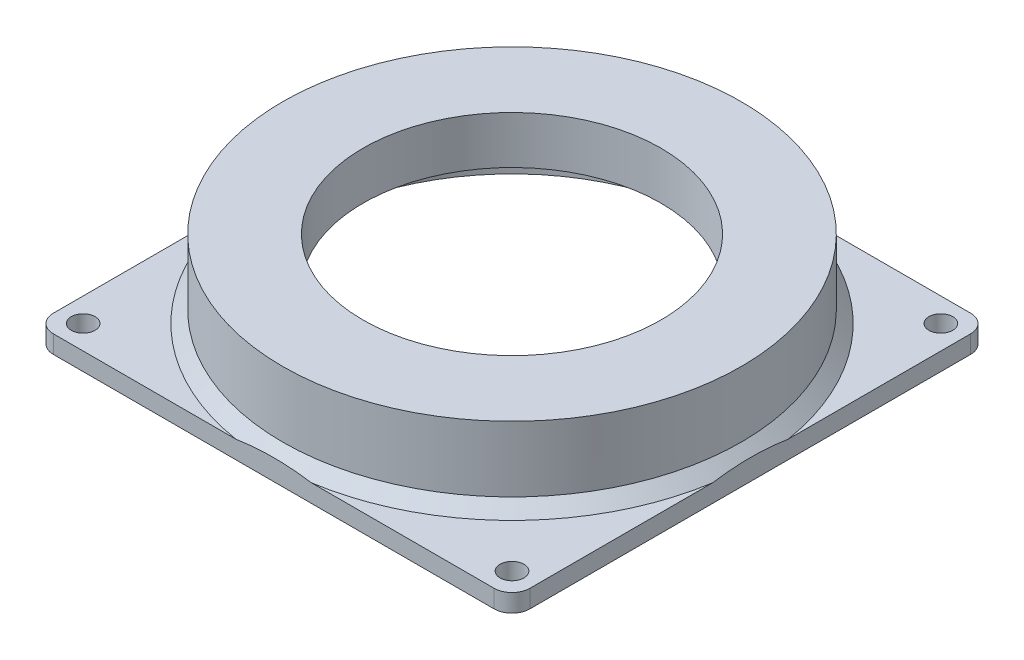
SolidWorks part; units mm, degrees
ref_plane "Front Plane" through (0, 0, 0) normal (0, 0, 1) x (1, 0, 0)
ref_plane "Top Plane" through (0, 0, 0) normal (0, 1, 0) x (1, 0, 0)
ref_plane "Right Plane" through (0, 0, 0) normal (1, 0, 0) x (0, 0, -1)
sketch "Sketch1" plane through (0, 0, 0) normal (0, 1, 0) x (1, 0, 0)
  line L1 (-40, 40) -> (40, 40)
  line L2 (-40, 40) -> (-40, -40)
  line L3 (-40, -40) -> (40, -40)
  line L4 (40, 40) -> (40, -40)
  line L5 (-40, 40) -> (40, -40) construction
  line L6 (-40, -40) -> (40, 40) construction
  point P0 (0, 0)
  dimension "D1" = 80
  dimension "D2" = 80
extrude "Boss-Extrude1" add sketch "Sketch1" along normal blind 3
fillet "Fillet1" radius 3 4 edges at (-40, 1.5, -40) (40, 1.5, -40) (40, 1.5, 40) (-40, 1.5, 40)
sketch "Sketch2" plane through (0, 3, 0) normal (0, 1, 0) x (1, 0, 0)
  line L0 (37, 40) -> (-37, 40) construction
  line L1 (40, -37) -> (40, 37) construction
  line L2 (-40, 37) -> (-40, -37) construction
  line L3 (-37, -40) -> (37, -40) construction
  circle A0 centre (-36, 36) radius 2
  circle A1 centre (36, 36) radius 2
  circle A2 centre (-36, -36) radius 2
  circle A3 centre (36, -36) radius 2
  dimension "D1" = 4
  dimension "D2" = 4
  dimension "D3" = 4
  dimension "D4" = 4
  dimension "D5" = 4
  dimension "D6" = 4
  dimension "D7" = 4
  dimension "D8" = 4
  dimension "D9" = 4
  dimension "D10" = 4
  dimension "D11" = 4
  dimension "D12" = 4
extrude "Cut-Extrude1" cut sketch "Sketch2" against normal blind 3
sketch "Sketch3" plane through (0, 3, 0) normal (0, 1, 0) x (1, 0, 0)
  circle A0 centre (0, 0) radius 35
  dimension "D1" = 70
extrude "Cut-Extrude2" cut sketch "Sketch3" against normal blind 3
sketch "Sketch4" plane through (0, 3, 0) normal (0, 1, 0) x (1, 0, 0)
  circle A0 centre (0, 0) radius 38.5
  circle A1 centre (0, 0) radius 35
  dimension "D1" = 3.5
extrude "Boss-Extrude2" add sketch "Sketch4" along normal blind 10
sketch "Sketch5" plane through (0, 13, 0) normal (0, 1, 0) x (1, 0, 0)
  circle A0 centre (0, 0) radius 38.5
extrude "Boss-Extrude3" add sketch "Sketch5" along normal blind 3
sketch "Sketch6" plane through (0, 16, 0) normal (0, 1, 0) x (1, 0, 0)
  circle A0 centre (0, 0) radius 25
  dimension "D1" = 50
extrude "Cut-Extrude3" cut sketch "Sketch6" against normal blind 3
sketch "Sketch7" plane through (0, 13, 0) normal (0, -1, 0) x (1, 0, 0)
  circle A0 centre (0, 0) radius 28.5
  circle A1 centre (0, 0) radius 25
  dimension "D1" = 3.5
extrude "Boss-Extrude4" add sketch "Sketch7" along normal blind 5
chamfer "Chamfer1" distance 2 angle 45 1 edges at (0, 13, 28.5)
chamfer "Chamfer2" distance 2 angle 45 1 edges at (0, 3, 38.5)
